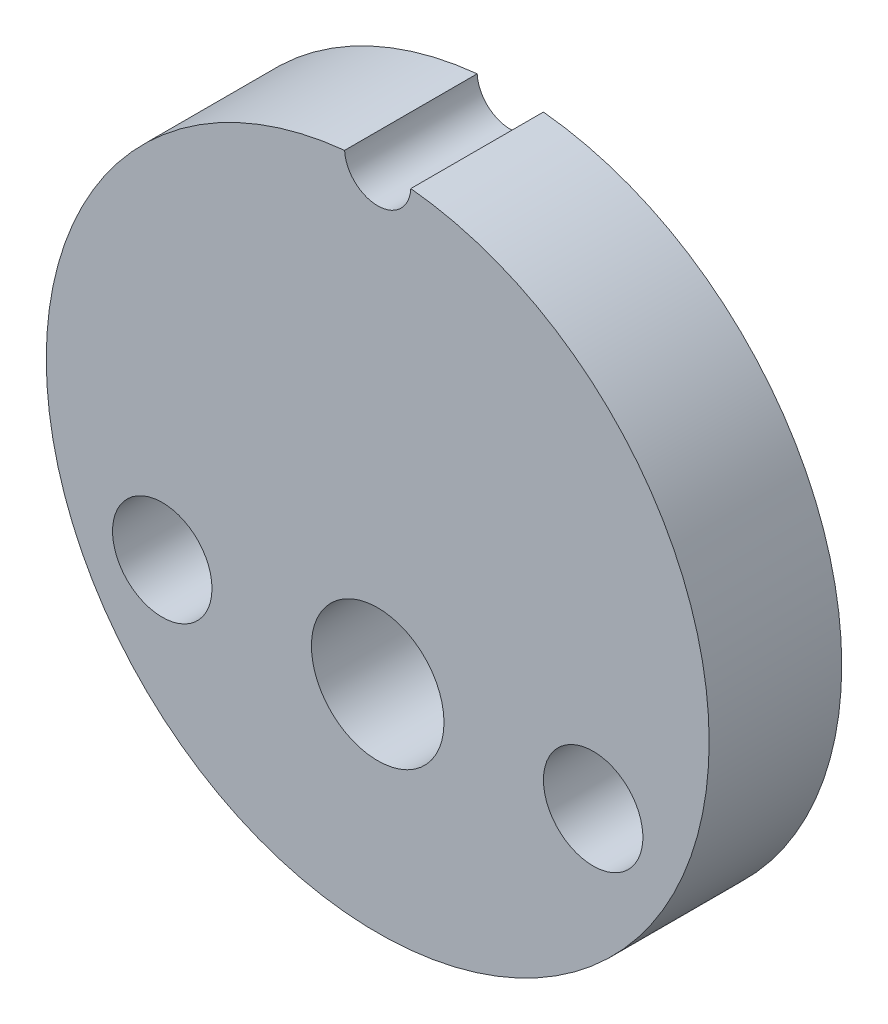
SolidWorks part; units mm, degrees
ref_plane "前视基准面" through (0, 0, 0) normal (0, 0, 1) x (1, 0, 0)
ref_plane "上视基准面" through (0, 0, 0) normal (0, 1, 0) x (1, 0, 0)
ref_plane "右视基准面" through (0, 0, 0) normal (1, 0, 0) x (0, 0, -1)
sketch "草图1" plane through (0, 0, 0) normal (0, 0, 1) x (1, 0, 0)
  line L0 (-0.5899, 5.3428) -> (-0.5899, 1.8428) construction
  line L1 (-0.5899, 1.8428) -> (-7.0899, 1.8428) construction
  circle A1 centre (-7.0899, 1.8428) radius 1.5
  circle A2 centre (5.9101, 1.8428) radius 1.5
  circle A3 centre (-0.5899, 1.8428) radius 2
  circle A4 centre (-0.5899, 5.3428) radius 10
  dimension "D1" = 3.5
  dimension "D2" = 6.5
extrude "凸台-拉伸1" add sketch "草图1" along normal blind 4
sketch "草图2" plane through (0, 0, 4) normal (0, 0, 1) x (1, 0, 0)
  circle A0 centre (-0.5899, 15.3428) radius 1
  circle A1 centre (-0.5899, 5.3428) radius 10 construction
extrude "切除-拉伸1" cut sketch "草图2" against normal blind 10
